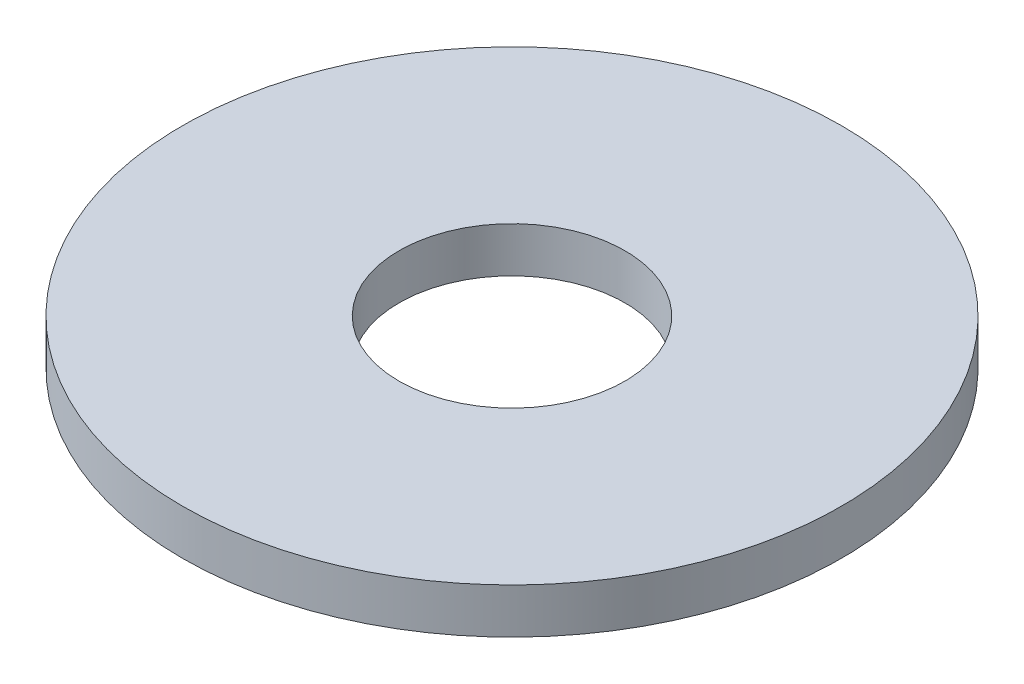
SolidWorks part; units mm, degrees
ref_plane "Front Plane" through (0, 0, 0) normal (0, 0, 1) x (1, 0, 0)
ref_plane "Top Plane" through (0, 0, 0) normal (0, 1, 0) x (1, 0, 0)
ref_plane "Right Plane" through (0, 0, 0) normal (1, 0, 0) x (0, 0, -1)
sketch "Sketch1" plane through (0, 0, 0) normal (0, 1, 0) x (1, 0, 0)
  circle A0 centre (0, 0) radius 87.5
  dimension "FLANGE_OD" = 175
extrude "Boss-Extrude1" add sketch "Sketch1" along normal blind 12
sketch "Sketch2" plane through (0, 0, 0) normal (0, 1, 0) x (1, 0, 0)
  circle A0 centre (0, 0) radius 30
  dimension "BORE_D" = 60
extrude "Cut-Extrude1" cut sketch "Sketch2" along normal through all
sketch "Sketch3" plane through (0, 12, 0) normal (0, 1, 0) x (1, 0, 0)
  circle A0 centre (0, 0) radius 23.2887 construction
  circle A1 centre (-23.2887, 0) radius 5.5255
  dimension "BOLT_D" = 11.0509
  dimension "BOLT_PCD" = 46.5773
extrude "Cut-Extrude2" cut sketch "Sketch3" against normal blind 8.5811 rebuild error yes
pattern_circular "CirPattern1" count 6 over 360 rebuild error yes
